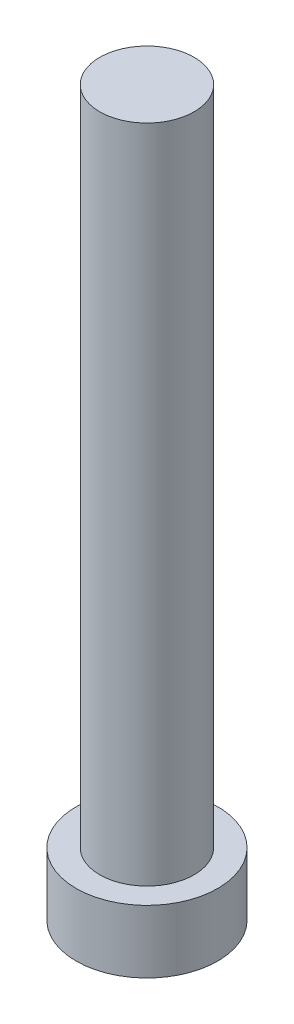
SolidWorks part; units mm, degrees
ref_plane "Front Plane" through (0, 0, 0) normal (0, 0, 1) x (1, 0, 0)
ref_plane "Top Plane" through (0, 0, 0) normal (0, 1, 0) x (1, 0, 0)
ref_plane "Right Plane" through (0, 0, 0) normal (1, 0, 0) x (0, 0, -1)
sketch "Sketch1" plane through (0, 0, 0) normal (0, 1, 0) x (1, 0, 0)
  circle A0 centre (0, 0) radius 22.5
  circle A1 centre (0, 0) radius 15
  dimension "D1" = 45
  dimension "D2" = 30
extrude "Boss-Extrude1" add sketch "Sketch1" along normal blind 230 contours A1
extrude "Boss-Extrude2" add sketch "Sketch1<4>" along normal blind 20
sketch "Sketch1<4>" plane through (0, 0, 0) normal (0, 1, 0) x (1, 0, 0) same geometry as "Sketch1"
